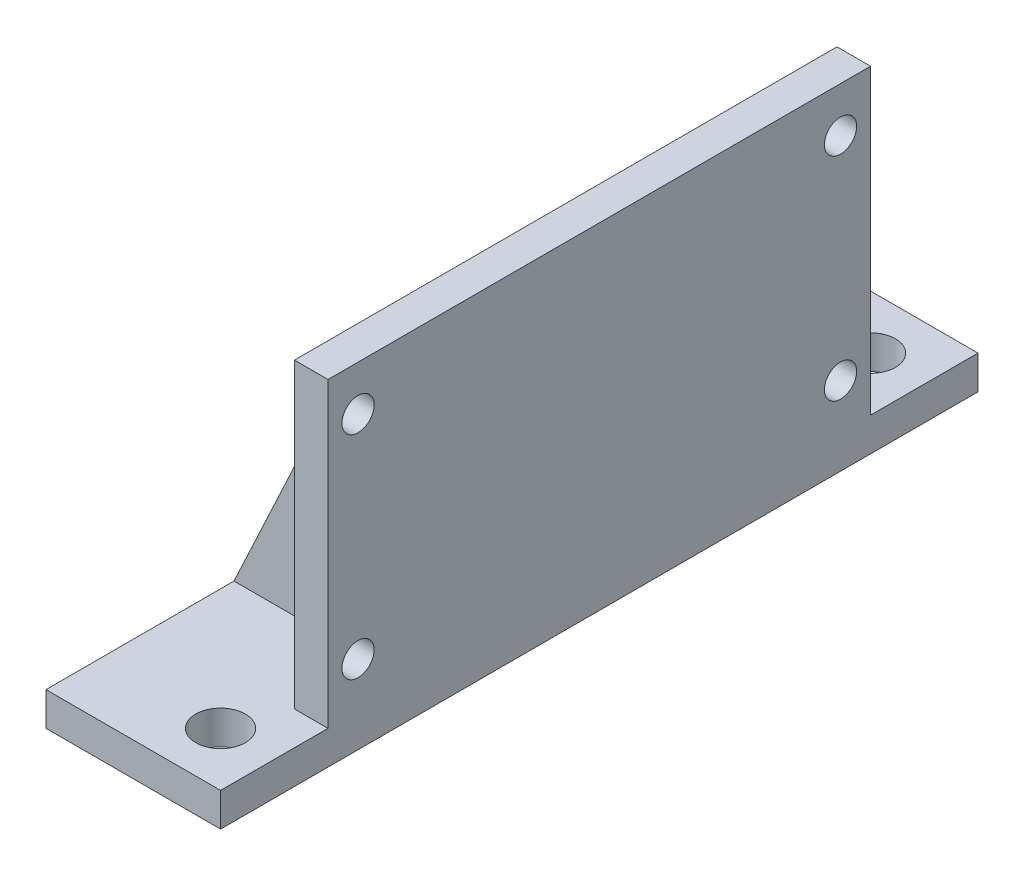
SolidWorks part; units mm, degrees
ref_plane "Front Plane" through (0, 0, 0) normal (0, 0, 1) x (1, 0, 0)
ref_plane "Top Plane" through (0, 0, 0) normal (0, 1, 0) x (1, 0, 0)
ref_plane "Right Plane" through (0, 0, 0) normal (1, 0, 0) x (0, 0, -1)
sketch "Sketch1" plane through (0, 0, 0) normal (0, 1, 0) x (1, 0, 0)
  line L0 (0, 0) -> (0, 61.4723)
  line L2 (0, 0) -> (-5.08, 0)
  line L3 (0, 0) -> (0, 5.08)
  line L4 (0, 5.08) -> (-5.08, 5.08)
  line L5 (-5.08, 0) -> (-5.08, 5.08)
  line L6 (-5.08, 5.08) -> (5.08, 5.08)
  line L7 (-5.08, 5.08) -> (-5.08, -5.08)
  line L8 (-5.08, -5.08) -> (5.08, -5.08)
  line L9 (5.08, 5.08) -> (5.08, -5.08)
  line L10 (0, 61.4723) -> (5.08, 61.4723)
  line L11 (0, 61.4723) -> (0, 56.3923)
  line L12 (0, 56.3923) -> (5.08, 56.3923)
  line L13 (5.08, 61.4723) -> (5.08, 56.3923)
  line L14 (5.08, 56.3923) -> (-5.08, 56.3923)
  line L15 (5.08, 56.3923) -> (5.08, 66.5523)
  line L16 (5.08, 66.5523) -> (-5.08, 66.5523)
  line L17 (-5.08, 56.3923) -> (-5.08, 66.5523)
  line L18 (-5.08, 56.3923) -> (5.08, 56.3923)
  line L19 (-5.08, 56.3923) -> (-5.08, 5.08)
  line L20 (-5.08, 5.08) -> (5.08, 5.08)
  line L21 (5.08, 56.3923) -> (5.08, 5.08)
  line L22 (-5.08, 66.5523) -> (-11.43, 66.5523)
  line L23 (-5.08, 66.5523) -> (-5.08, -5.08)
  line L24 (-5.08, -5.08) -> (-11.43, -5.08)
  line L25 (-11.43, 66.5523) -> (-11.43, -5.08)
  circle A1 centre (0, 61.4723) radius 2.3495
  circle A2 centre (0, 0) radius 2.3495
  dimension "D2" = 4.699
  dimension "D3" = 4.699
  dimension "D1" = 61.4723
  dimension "D4" = 5.08
  dimension "D5" = 10.16
  dimension "D6" = 5.08
  dimension "D7" = 10.16
  dimension "D8" = 6.35
extrude "Boss-Extrude1" add sketch "Sketch1" along normal blind 3.175 contours A1 L10 L15 L16 L17 L14 L0 | A1 L0 L12 L13 L10 | L14 L19 L4 L0 | L21 L12 L0 L6 | A2 L3 L4 L5 L2 | A2 L2 L7 L8 L9 L6 L3 | L22 L25 L24 L7 L5 L19 L17 region at (-2.54, 0, -30.7361) region at (2.54, 0, -4.9363) region at (-2.8515, 0, -2.8515) region at (2.54, 0, -30.7361) region at (-2.54, 0, -56.536) region at (2.8515, 0, -58.6207) region at (-8.255, 0, -30.7361)
sketch "Sketch2" plane through (5.08, 0, 0) normal (1, 0, 0) x (0, 0, -1)
  line L1 (5.08, 3.175) -> (56.3923, 3.175)
  line L2 (5.08, 3.175) -> (5.08, 31.75)
  line L3 (5.08, 31.75) -> (56.3923, 31.75)
  line L4 (56.3923, 3.175) -> (56.3923, 31.75)
  line L5 (66.5523, 3.175) -> (66.5523, 0)
  line L6 (-5.08, 3.175) -> (66.5523, 3.175) construction
  line L7 (-5.08, 3.175) -> (66.5523, 3.175)
  line L8 (7.9214, 27.4955) -> (7.9214, 7.4295) construction
  line L9 (7.9214, 7.4295) -> (24.6813, 7.4295) construction
  line L10 (53.5509, 27.4955) -> (53.5509, 7.4295) construction
  line L11 (7.9214, 17.4625) -> (53.5509, 17.4625) construction
  line L12 (5.08, 31.75) -> (56.3923, 3.175) construction
  line L13 (30.7361, 17.4625) -> (44.0356, 17.4625) construction
  circle A0 centre (7.9214, 27.4955) radius 1.524
  circle A1 centre (53.5509, 27.4955) radius 1.524
  circle A2 centre (53.5509, 7.4295) radius 1.524
  circle A3 centre (7.9214, 7.4295) radius 1.524
  line M5 (66.5523, 3.175) -> (-5.08, 3.175)
  dimension "D2" = 3.048
  dimension "D3" = 3.048
  dimension "D4" = 3.048
  dimension "D5" = 3.048
  dimension "D1" = 28.575
  dimension "D6" = 10.16
  dimension "D7" = 10.16
  dimension "D8" = 20.066
  dimension "D9" = 45.6295
  dimension "D10" = 20.066
extrude "Boss-Extrude2" add sketch "Sketch2" against normal blind 3.175 contours L4 L3 L2 A3 A2 A1 A0 M5 region at (5.08, 17.4625, -30.7361)
ref_plane "Plane1" through (0, 0, -30.7361) normal (0, 0, 1) x (1, 0, 0)
ref_plane "Plane2" through (0, 0, -48.7723) normal (0, 0, -1) x (-1, 0, 0)
sketch "Sketch3" plane through (0, 0, -48.7723) normal (0, 0, -1) x (-1, 0, 0)
  line L0 (-1.905, 3.175) -> (-1.905, 31.75) construction
  line L1 (-1.905, 3.175) -> (-1.905, 31.75)
  line L2 (-5.08, 3.175) -> (11.43, 3.175) construction
  line L3 (-5.08, 3.175) -> (11.43, 3.175)
  line L4 (-1.905, 31.75) -> (11.43, 3.175)
extrude "Boss-Extrude3" add sketch "Sketch3" against normal blind 2.54 contours L4 L1 L3 region at (-2.54, 12.7, -48.7723)
mirror "Mirror1" about plane through (0, 0, -30.7361) normal (0, 0, 1) of "Boss-Extrude3"
